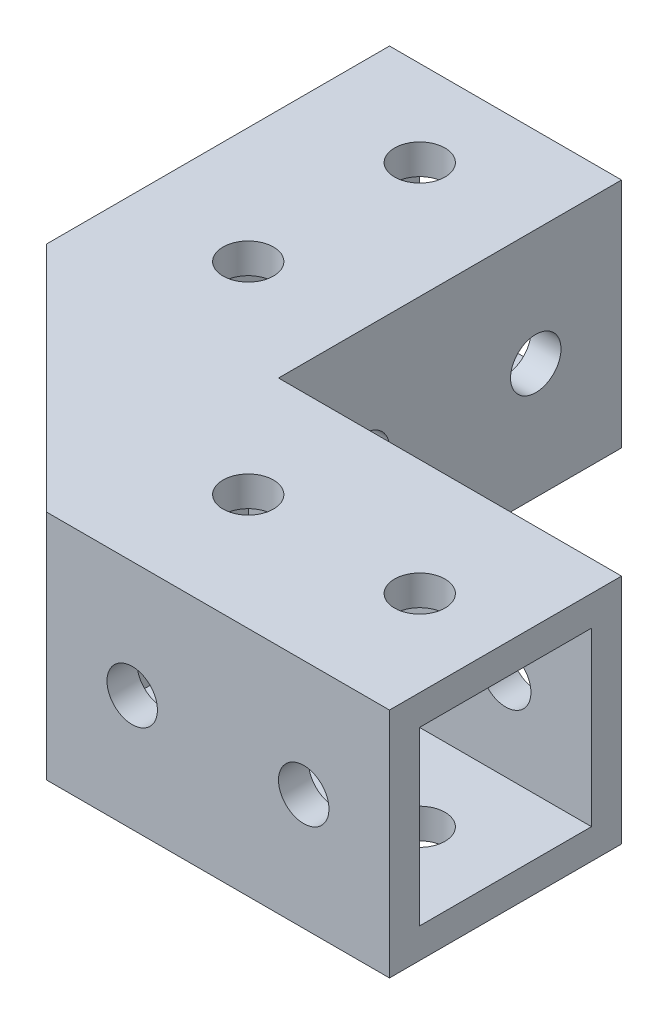
SolidWorks part; units mm, degrees
ref_plane "Front Plane" through (0, 0, 0) normal (0, 0, 1) x (1, 0, 0)
ref_plane "Top Plane" through (0, 0, 0) normal (0, 1, 0) x (1, 0, 0)
ref_plane "Right Plane" through (0, 0, 0) normal (1, 0, 0) x (0, 0, -1)
other "Configuration Table"
sketch "sketch1" plane through (0, 0, 0) normal (0, 1, 0) x (1, 0, 0)
  line L0 (0, -11.5) -> (8.5, -11.5) construction
  line L1 (0, 0) -> (34, 0)
  line L2 (0, 0) -> (0, -23)
  line L3 (0, -23) -> (34, -23)
  line L4 (34, 0) -> (34, -23)
  line L5 (8.5, -11.5) -> (25.5, -11.5) construction
  circle A1 centre (8.5, -11.5) radius 2.5
  circle A2 centre (25.5, -11.5) radius 2.5
  dimension "D4" = 5
  dimension "D1" = 23
  dimension "D2" = 34
  dimension "D3" = 8.5
  dimension "D6" = 17
extrude "Boss-Extrude1" add sketch "sketch1" along normal blind 23
sketch "Sketch6" plane through (0, 0, 0) normal (0, 0, -1) x (-1, 0, 0)
  line L0 (-34, 11.5) -> (-25.5, 11.5) construction
  line L1 (-25.5, 11.5) -> (-8.5, 11.5) construction
  line L4 (-34, 0) -> (0, 0)
  line L5 (0, 0) -> (0, 23)
  line L6 (0, 23) -> (-34, 23)
  line L7 (-34, 23) -> (-34, 0)
  line L8 (-34, 0) -> (0, 0)
  line L9 (0, 0) -> (0, 23)
  line L10 (0, 23) -> (-34, 23)
  line L11 (-34, 23) -> (-34, 0)
  circle A0 centre (-25.5, 11.5) radius 2.5
  circle A1 centre (-8.5, 11.5) radius 2.5
  dimension "D3" = 5
  dimension "D2" = 8.5
  dimension "D5" = 17
extrude "Cut-Extrude10" cut sketch "Sketch6" against normal through all flip side to cut
sketch "Sketch7" plane through (34, 0, 0) normal (1, 0, 0) x (0, 0, -1)
  line L0 (-23, 11.5) -> (0, 11.5) construction
  line L4 (-23, 0) -> (0, 0)
  line L5 (0, 0) -> (0, 23)
  line L6 (0, 23) -> (-23, 23)
  line L7 (-23, 23) -> (-23, 0)
  line L8 (-23, 0) -> (0, 0)
  line L9 (0, 0) -> (0, 23)
  line L10 (0, 23) -> (-23, 23)
  line L11 (-23, 23) -> (-23, 0)
  line L14 (-20.02, 20.02) -> (-2.98, 20.02)
  line L15 (-20.02, 20.02) -> (-20.02, 2.98)
  line L16 (-20.02, 2.98) -> (-2.98, 2.98)
  line L17 (-2.98, 20.02) -> (-2.98, 2.98)
  line L18 (-20.02, 20.02) -> (-2.98, 2.98) construction
  line L19 (-20.02, 2.98) -> (-2.98, 20.02) construction
  point P6 (-11.5, 11.5)
  dimension "D2" = 17.04
extrude "Cut-Extrude11" cut sketch "Sketch7" against normal blind 34 flip side to cut
sketch "Sketch9" plane through (0, 0, 0) normal (0, 1, 0) x (1, 0, 0)
  line L0 (0, 0) -> (34, 0) construction
  line L1 (0, 0) -> (24.0416, 24.0416) construction
  dimension "D1" = 45
ref_plane "Plane2" through (0, 0, 0) normal (-0.7071, 0, -0.7071) x (-0.7071, 0, 0.7071)
mirror "Mirror6" about plane through (0, 0, 0) normal (-0.7071, 0, -0.7071) of bodies 118 110
sketch "Sketch11" plane through (0, 0, 0) normal (0, 1, 0) x (1, 0, 0)
  line L0 (-23, 0) -> (0, -23)
  line L1 (0, 0) -> (-23, 0) construction
  line L2 (0, 0) -> (0, -23) construction
  line L3 (0, 0) -> (-23, 0)
  line L4 (0, 0) -> (0, -23)
extrude "Boss-Extrude2" add sketch "Sketch11" along normal blind 23
sketch "Sketch13" plane through (0, 0, 0) normal (0, 1, 0) x (1, 0, 0)
  line L0 (-11.5, 8.5) -> (5.1708, 5.1708) construction
  line L1 (0, 0) -> (24.0416, 24.0416) construction
  line L2 (5.1708, 5.1708) -> (8.5, -11.5) construction
  line L4 (8.7064, 8.7064) -> (0, 17)
  line L5 (0, 34) -> (0, 0) construction
  line L6 (8.7064, 8.7064) -> (17, 0)
  line L7 (0, 0) -> (34, 0) construction
  line L8 (0, 0) -> (24.0416, 24.0416) construction
  line L9 (0, 17) -> (0, 0)
  line L10 (0, 0) -> (17, 0)
  circle A0 centre (8.5, -11.5) radius 2.5 construction
  circle A1 centre (-11.5, 8.5) radius 2.5 construction
  circle A2 centre (8.5, -11.5) radius 2.5 construction
  circle A3 centre (-11.5, 8.5) radius 2.5 construction
  circle A4 centre (5.1708, 5.1708) radius 2.5
  dimension "D3" = 5
  dimension "D2" = 5
  dimension "D1" = 17
  dimension "D4" = 17
extrude "Boss-Extrude3" add sketch "Sketch13" along normal blind 4
equation "\"D2@sketch1\" = \"length\""
equation "\"holes\"= 2'Holes per side"
equation "\"cdist\"= 17mm'centre distance between holes"
equation "\"width\"= \"insetwidth\" + 2 * \"shellwidth\""
equation "\"length\"= \"cdist\" * \"holes\""
equation "\"D1@sketch1\"=\"width\""
equation "\"hdiam\"= 5mm'Hole diametre"
equation "\"D4@sketch1\" = \"hdiam\""
equation "\"D6@sketch1\" = \"cdist\""
equation "\"D5@sketch1\" = \"holes\""
equation "\"D2@Sketch6\"=\"cdist\"/2"
equation "\"D3@Sketch6\"=\"hdiam\""
equation "\"D5@Sketch6\"=\"cdist\""
equation "\"D4@Sketch6\"=\"holes\""
equation "\"D1@Boss-Extrude1\"=\"width\""
equation "\"joint\"= 90"
equation "\"D1@Sketch9\"=\"joint\"/2"
equation "\"D1@Boss-Extrude2\"=\"width\""
equation "\"D2@Sketch13\"=\"hdiam\""
equation "\"D4@Sketch13\"=\"cdist\""
equation "\"D1@Boss-Extrude3\"=\"supportheight\""
equation "\"supportheight\"= 4mm"
equation "\"tolerance\"= 0.04mm"
equation "\"insetwidth\"= 17mm"
equation "\"D1@Cut-Extrude11\"=\"length\""
equation "\"true\"= 1"
equation "\"false\"= 0"
equation "\"supportenabled\"= \"true\""
equation "\"Boss-Extrude3\"= IIF ( \"supportenabled\" < \"true\" , \"suppressed\" , \"unsuppressed\" )"
equation "\"D2@Sketch7\"=\"insetwidth\"+\"tolerance\""
equation "\"shellwidth\"= 3mm"
